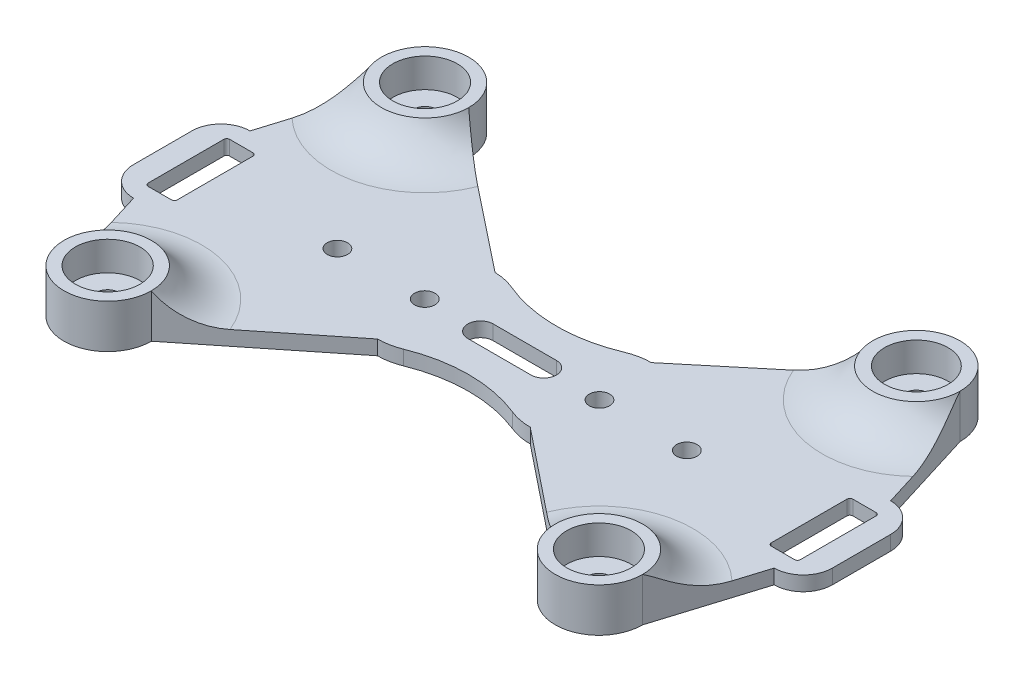
SolidWorks part; units mm, degrees
ref_plane "Front Plane" through (0, 0, 0) normal (0, 0, 1) x (1, 0, 0)
ref_plane "Top Plane" through (0, 0, 0) normal (0, 1, 0) x (1, 0, 0)
ref_plane "Right Plane" through (0, 0, 0) normal (1, 0, 0) x (0, 0, -1)
sketch "Sketch1" plane through (0, 0, 0) normal (0, 1, 0) x (1, 0, 0)
  line L0 (-5.4293, 0) -> (5.4293, 0) construction
  line L6 (-60, -5) -> (-60, 5)
  line L18 (60, -5) -> (60, 5)
  line L19 (-5.4293, 2.1756) -> (5.4293, 2.1756)
  line L20 (-5.4293, -2.1756) -> (5.4293, -2.1756)
  line L21 (-55, 10) -> (-11, 10)
  line L22 (-11, -10) -> (-55, -10)
  line L23 (11, -10) -> (55, -10)
  line L24 (11.7144, 10) -> (55, 10)
  line L26 (-55.5, -7) -> (-51.5, -7)
  line L27 (-56, -6.5) -> (-56, 6.5)
  line L28 (-55.5, 7) -> (-51.5, 7)
  line L29 (-51, -6.5) -> (-51, 6.5)
  line L30 (51.5, -7) -> (55.5, -7)
  line L31 (51, -6.5) -> (51, 6.5)
  line L32 (51.5, 7) -> (55.5, 7)
  line L33 (56, -6.5) -> (56, 6.5)
  circle A12 centre (-30, 0) radius 1.75
  circle A13 centre (-15, 0) radius 1.75
  circle A14 centre (30, 0) radius 1.75
  circle A15 centre (15, 0) radius 1.75
  arc A16 (55, -10) -> (60, -5) centre (55, -5) ccw
  arc A17 (55, 10) -> (60, 5) centre (55, 5) cw
  arc A18 (-55, -10) -> (-60, -5) centre (-55, -5) cw
  arc A19 (-60, 5) -> (-55, 10) centre (-55, 5) cw
  arc A20 (-5.4293, 2.1756) -> (-5.4293, -2.1756) centre (-5.4293, 0) ccw
  arc A21 (5.4293, -2.1756) -> (5.4293, 2.1756) centre (5.4293, 0) ccw
  arc A22 (-11, 10) -> (11.7144, 10) centre (0.3572, 32.2714) ccw
  arc A23 (-11, -10) -> (11, -10) centre (0, -32.4499) cw
  arc A24 (51, -6.5) -> (51.5, -7) centre (51.5, -6.5) ccw
  arc A25 (56, -6.5) -> (55.5, -7) centre (55.5, -6.5) cw
  arc A26 (51.5, 7) -> (51, 6.5) centre (51.5, 6.5) ccw
  arc A27 (55.5, 7) -> (56, 6.5) centre (55.5, 6.5) cw
  arc A28 (-55.5, -7) -> (-56, -6.5) centre (-55.5, -6.5) cw
  arc A29 (-51.5, -7) -> (-51, -6.5) centre (-51.5, -6.5) ccw
  arc A30 (-51.5, 7) -> (-51, 6.5) centre (-51.5, 6.5) cw
  arc A31 (-56, 6.5) -> (-55.5, 7) centre (-55.5, 6.5) cw
  point P0 (0, 0)
  point P23 (0, 0)
  point P47 (56, -7)
  point P50 (51, 7)
  point P53 (56, 7)
  point P56 (-56, -7)
  point P61 (-51, 7)
  point P64 (-56, 7)
  dimension "D3" = 3.5
  dimension "D4" = 3.5
  dimension "D5" = 3.5
  dimension "D6" = 3.5
  dimension "D7" = 15
  dimension "D16" = 14
  dimension "D17" = 3
  dimension "D15" = 5
  dimension "D2" = 25
  dimension "D11" = 25
  dimension "D21" = 0.5
  dimension "D8" = 15
  dimension "D9" = 15
  dimension "D10" = 15
  dimension "D12" = 5
  dimension "D13" = 5
  dimension "D14" = 14
  dimension "D18" = 3
  dimension "D19" = 4
  dimension "D20" = 4
extrude "Boss-Extrude2" add sketch "Sketch1" along normal blind 2.5
fillet "Fillet3" radius 10 2 edges at (11, 1.25, 10) (-11, 1.25, 10)
fillet "Fillet4" radius 10 2 edges at (11.7144, 1.25, -10) (-11, 1.25, -10)
sketch "Sketch2" plane through (0, 2.5, 0) normal (0, 1, 0) x (1, 0, 0)
  circle A0 centre (-42.2, 27.25) radius 2
  circle A5 centre (42.1596, 27.25) radius 2
  circle A6 centre (-42.2, -27.25) radius 2
  circle A7 centre (42.1596, -27.25) radius 2
  circle A8 centre (42.1596, -27.25) radius 7.5
  circle A9 centre (42.1596, 27.25) radius 7.5
  circle A10 centre (-42.2, 27.25) radius 7.5
  circle A11 centre (-42.2, -27.25) radius 7.5
  dimension "D18" = 4
  dimension "D19" = 4
  dimension "D20" = 4
  dimension "D21" = 4
  dimension "D23" = 15
  dimension "D24" = 15
extrude "Boss-Extrude3" add sketch "Sketch2" against normal through all separate body
sketch "Sketch3" plane through (0, 2.5, 0) normal (0, 1, 0) x (1, 0, 0)
  line L0 (-49.7, 27.25) -> (-55, 10)
  line L1 (-13.1912, 10) -> (-55, 10) construction
  line L3 (-55, -10) -> (-49.7, -27.25)
  line L9 (55, 10) -> (13.9056, 10) construction
  line L11 (13.1149, -10) -> (55, -10) construction
  line L13 (49.6596, -27.25) -> (55, -10)
  line L15 (55, 10) -> (49.6596, 27.25)
  line L20 (34.6596, -27.25) -> (13.1149, -10)
  line L21 (13.1149, -10) -> (55, -10)
  line L22 (34.6596, 27.25) -> (13.9056, 10)
  line L23 (13.9056, 10) -> (55, 10)
  line L24 (-34.7, 27.25) -> (-12.9219, 9.9964)
  line L25 (-12.9219, 9.9964) -> (-55, 10)
  line L26 (-34.7, -27.25) -> (-13.1149, -10)
  line L27 (-13.1149, -10) -> (-55, -10)
  circle A0 centre (-42.2, 27.25) radius 7.5 construction
  arc A1 (-55, 10) -> (-60, 5) centre (-55, 5) ccw construction
  circle A2 centre (-42.2, -27.25) radius 7.5 construction
  circle A3 centre (42.1596, 27.25) radius 7.5 construction
  circle A4 centre (42.1596, -27.25) radius 7.5 construction
  arc A5 (-34.7, 27.25) -> (-49.7, 27.25) centre (-42.2, 27.25) cw
  arc A6 (-49.7, -27.25) -> (-34.7, -27.25) centre (-42.2, -27.25) cw
  arc A7 (34.6596, -27.25) -> (49.6596, -27.25) centre (42.1596, -27.25) cw
  arc A8 (49.6596, 27.25) -> (34.6596, 27.25) centre (42.1596, 27.25) cw
  arc A10 (-9.3202, 9.2204) -> (-13.1912, 10) centre (-13.1912, 0) ccw construction
  dimension "D1" = 18.0458
extrude "Boss-Extrude4" add sketch "Sketch3" against normal blind 2.5
sketch "Sketch4" plane through (0, 2.5, 0) normal (0, 1, 0) x (1, 0, 0)
  circle A0 centre (-42.2, 27.25) radius 5.5335
  circle A1 centre (42.1596, 27.25) radius 5.46
  circle A2 centre (42.1596, -27.25) radius 5.5324
  circle A3 centre (-42.2, -27.25) radius 5.5476
  circle A4 centre (-42.2, 27.25) radius 7.5
  circle A5 centre (42.1596, 27.25) radius 7.5
  circle A6 centre (42.1596, -27.25) radius 7.5
  circle A7 centre (-42.2, -27.25) radius 7.5
extrude "Boss-Extrude5" add sketch "Sketch4" along normal blind 5
fillet "Fillet5" radius 10 4 edges at (-42.2, 2.5, 19.75) (42.1596, 2.5, 19.75) (42.1596, 2.5, -19.75) (-42.2, 2.5, -19.75)
